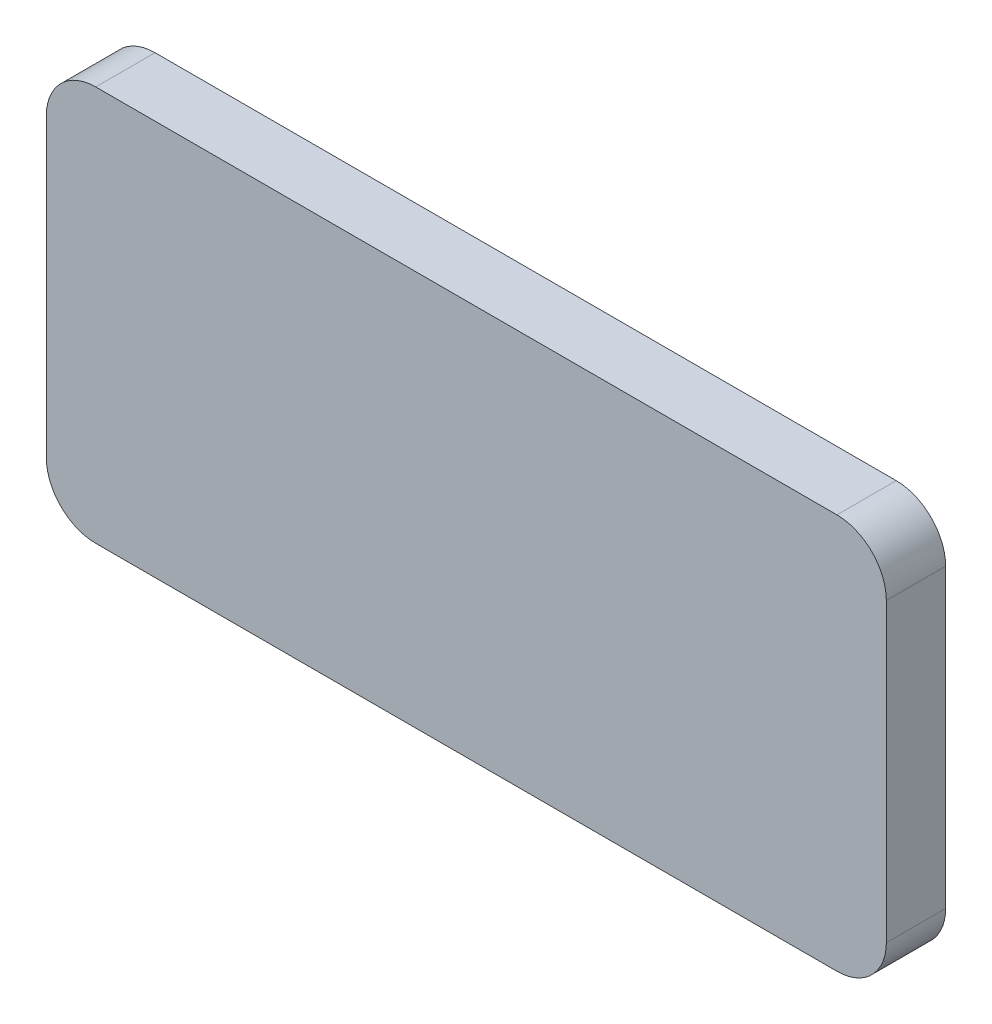
SolidWorks part; units mm, degrees
ref_plane "Plan de face" through (0, 0, 0) normal (0, 0, 1) x (1, 0, 0)
ref_plane "Plan de dessus" through (0, 0, 0) normal (0, 1, 0) x (1, 0, 0)
ref_plane "Plan de droite" through (0, 0, 0) normal (1, 0, 0) x (0, 0, -1)
sketch "Esquisse1" plane through (0, 0, 0) normal (0, 0, 1) x (1, 0, 0)
  line L1 (0, 0) -> (85, 0)
  line L2 (0, 0) -> (0, 40)
  line L3 (0, 40) -> (85, 40)
  line L4 (85, 0) -> (85, 40)
  dimension "D1" = 85
  dimension "D2" = 40
extrude "Boss.-Extru.1" add sketch "Esquisse1" along normal blind 6
fillet "Congé1" radius 5 4 edges at (0, 0, 3) (85, 0, 3) (85, 40, 3) (0, 40, 3)
sketch "Esquisse2" plane through (0, 0, 0) normal (0, 0, -1) x (-1, 0, 0)
  line L0 (0, 35) -> (0, 5) construction
  line L1 (-80, 40) -> (-5, 40) construction
  circle A0 centre (-9, 31) radius 4.5
  dimension "D1" = 9
  dimension "D2" = 9
  dimension "D3" = 9
extrude "Boss.-Extru.2" add sketch "Esquisse2" along normal blind 1
pattern_linear "Répétition linéaire1" count 7 spacing 11 along (1, 0, 0) count 3 spacing 11 along (0, -1, 0) of "Boss.-Extru.2"
fillet "Congé2" radius 5 21 edges at (70.5, 31, -1) (70.5, 20, -1) (70.5, 9, -1) (59.5, 9, -1) (59.5, 20, -1) (59.5, 31, -1) (48.5, 31, -1) (48.5, 20, -1) (48.5, 9, -1) (37.5, 9, -1) (37.5, 20, -1) (37.5, 31, -1) (26.5, 31, -1) (26.5, 20, -1) (26.5, 9, -1) (15.5, 20, -1) (15.5, 9, -1) (4.5, 9, -1) (4.5, 20, -1) (4.5, 31, -1) (15.5, 31, -1)
